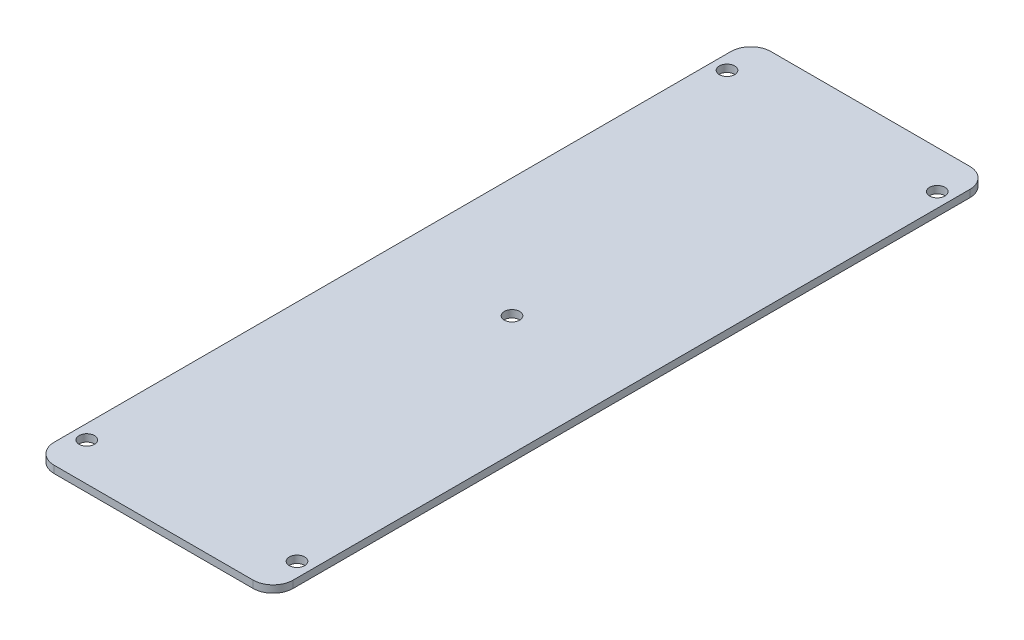
SolidWorks part; units mm, degrees
material "Glass Epoxy Composite"
ref_plane "Front Plane" through (0, 0, 0) normal (0, 0, 1) x (1, 0, 0)
ref_plane "Top Plane" through (0, 0, 0) normal (0, 1, 0) x (1, 0, 0)
ref_plane "Right Plane" through (0, 0, 0) normal (1, 0, 0) x (0, 0, -1)
sketch "Sketch1" plane through (0, 0, 0) normal (0, 1, 0) x (1, 0, 0)
  line L1 (0, 0) -> (50, 0)
  line L2 (0, 0) -> (0, -150)
  line L3 (0, -150) -> (50, -150)
  line L4 (50, 0) -> (50, -150)
  dimension "D1" = 50
  dimension "D2" = 150
extrude "Boss-Extrude1" add sketch "Sketch1" along normal blind 1.524
sketch "Sketch2" plane through (0, 1.524, 0) normal (0, 1, 0) x (1, 0, 0)
  line L0 (50, 0) -> (0, 0) construction
  line L1 (50, -150) -> (50, 0) construction
  circle A0 centre (47, -8) radius 1.6
  dimension "D1" = 3.2
  dimension "D2" = 8
  dimension "D3" = 3
extrude "Cut-Extrude1" cut sketch "Sketch2" against normal up to surface (1.524 mm away) up to face at (25, 0, 75)
pattern_linear "LPattern1" count 2 spacing 44 along (-1, 0, 0) count 2 spacing 134 along (0, 0, 1) of "Cut-Extrude1"
fillet "Fillet1" radius 4.191 4 edges at (50, 0.762, 150) (0, 0.762, 150) (0, 0.762, 0) (50, 0.762, 0)
sketch "Sketch3" plane through (0, 1.524, 0) normal (0, 1, 0) x (1, 0, 0)
  line L0 (25, -150) -> (25, -8) construction
  line L1 (4.191, -150) -> (45.809, -150) construction
  line L2 (3, -142) -> (47, -142) construction
  line L3 (47, -8) -> (3, -8) construction
  circle A0 centre (25, -75) radius 1.6
  dimension "D1" = 3.2
  dimension "D2" = 67
extrude "Cut-Extrude2" cut sketch "Sketch3" against normal up to surface (1.524 mm away) up to face at (3, 0, 9.6)
